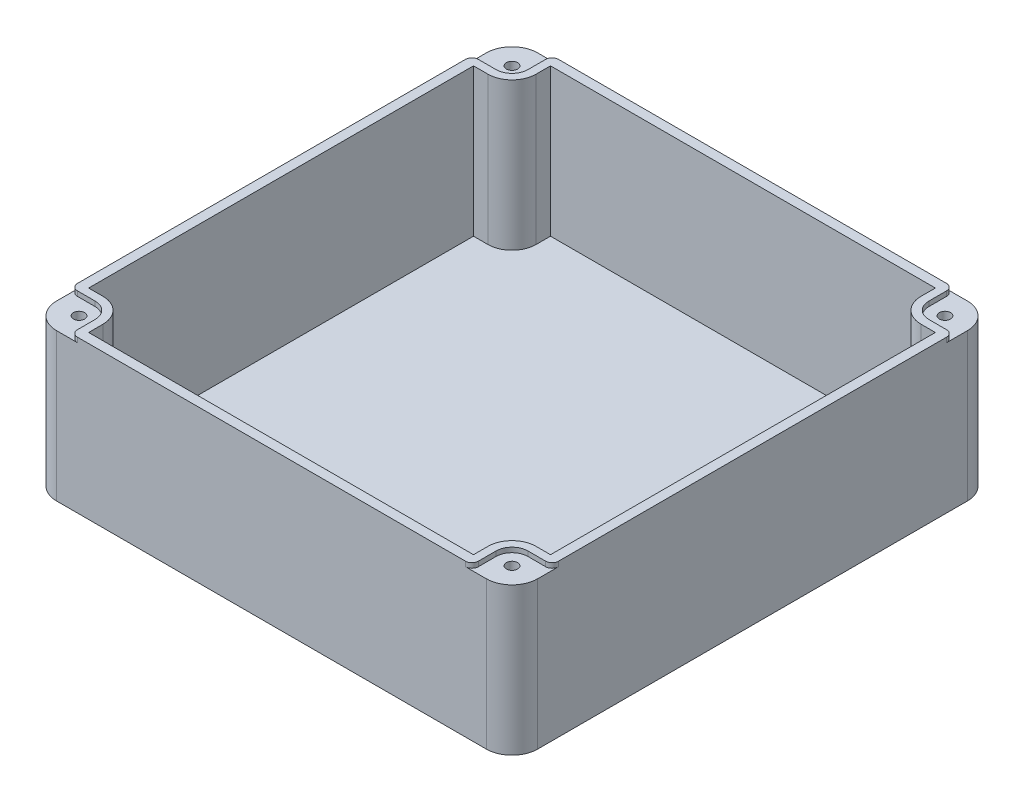
SolidWorks part; units mm, degrees
ref_plane "Front Plane" through (0, 0, 0) normal (0, 0, 1) x (1, 0, 0)
ref_plane "Top Plane" through (0, 0, 0) normal (0, 1, 0) x (1, 0, 0)
ref_plane "Right Plane" through (0, 0, 0) normal (1, 0, 0) x (0, 0, -1)
sketch "Sketch1" plane through (0, 0, 0) normal (0, 1, 0) x (1, 0, 0)
  line L0 (-72, -60) -> (-72, 60)
  line L1 (-67, -75) -> (67, -75)
  line L2 (-75, -67) -> (-75, 67)
  line L3 (-67, 75) -> (67, 75)
  line L4 (75, -67) -> (75, 67)
  line L5 (-75, -75) -> (75, 75) construction
  line L6 (-75, 75) -> (75, -75) construction
  line L7 (-60, 72) -> (60, 72)
  line L8 (72, -60) -> (72, 60)
  line L9 (-60, -72) -> (60, -72)
  line L10 (-62.5, 75) -> (-62.5, 67.5)
  line L11 (-67.5, 62.5) -> (-75, 62.5)
  line L12 (-67, 72) -> (67, 72) construction
  line L13 (-72, -67) -> (-72, 67) construction
  line L14 (-60, 72) -> (-60, 67.5)
  line L15 (-67.5, 60) -> (-72, 60)
  line L16 (62.5, 67.5) -> (62.5, 75)
  line L17 (75, 62.5) -> (67.5, 62.5)
  line L18 (72, 60) -> (67.5, 60)
  line L19 (60, 67.5) -> (60, 72)
  line L20 (67.5, -62.5) -> (75, -62.5)
  line L21 (62.5, -75) -> (62.5, -67.5)
  line L22 (60, -72) -> (60, -67.5)
  line L23 (67.5, -60) -> (72, -60)
  line L24 (-62.5, -67.5) -> (-62.5, -75)
  line L25 (-75, -62.5) -> (-67.5, -62.5)
  line L26 (-72, -60) -> (-67.5, -60)
  line L27 (-60, -67.5) -> (-60, -72)
  line L28 (-67.5, 62.5) -> (-72, 62.5) construction
  line L29 (72, -67) -> (72, 67) construction
  line L30 (-67, -72) -> (67, -72) construction
  line L31 (-62.5, 72) -> (-62.5, 67.5) construction
  arc A0 (-75, 67) -> (-67, 75) centre (-67, 67) cw
  arc A1 (67, 75) -> (75, 67) centre (67, 67) cw
  arc A2 (67, -75) -> (75, -67) centre (67, -67) ccw
  arc A3 (-67, -75) -> (-75, -67) centre (-67, -67) cw
  arc A4 (-62.5, 67.5) -> (-67.5, 62.5) centre (-67.5, 67.5) cw
  arc A5 (-60, 67.5) -> (-67.5, 60) centre (-67.5, 67.5) cw
  arc A6 (67.5, 62.5) -> (62.5, 67.5) centre (67.5, 67.5) cw
  arc A7 (67.5, 60) -> (60, 67.5) centre (67.5, 67.5) cw
  arc A8 (62.5, -67.5) -> (67.5, -62.5) centre (67.5, -67.5) cw
  arc A9 (60, -67.5) -> (67.5, -60) centre (67.5, -67.5) cw
  arc A10 (-67.5, -62.5) -> (-62.5, -67.5) centre (-67.5, -67.5) cw
  arc A11 (-67.5, -60) -> (-60, -67.5) centre (-67.5, -67.5) cw
  circle A12 centre (-67.5, 67.5) radius 1.75
  circle A13 centre (67.5, 67.5) radius 1.75
  circle A14 centre (67.5, -67.5) radius 1.75
  circle A15 centre (-67.5, -67.5) radius 1.75
  point P0 (0, 0)
  point P31 (-62.5, 62.5)
  point P70 (0, 0)
  dimension "D2" = 8
  dimension "D6" = 5
  dimension "D9" = 3.5
  dimension "D1" = 150
  dimension "D5" = 12.5
  dimension "D3" = 3
  dimension "D4" = 3
  dimension "D7" = 2.5
  dimension "D8" = 4
  dimension "D10" = 4
extrude "Boss-Extrude1" add sketch "Sketch1" against normal blind 46 contours L25 A10 L24 L1 L21 A8 L20 L4 L17 A6 L16 L3 L10 A4 L11 L2 A11 L26 L0 L15 A5 L14 L7 L19 A7 L18 L8 L23 A9 L22 L9 L27 | A8 L21 L1 A2 L4 L20 A14 | A10 L25 L2 A3 L1 L24 A15 | A4 L10 L3 A0 L2 L11 A12 | A6 L17 L4 A1 L3 L16 A13 | A14 | A15 | A12 | A13 region at (-72.5319, 0, 72.5319) region at (-60.3787, 0, 71.25) region at (62.6768, 0, 71.25) region at (-74.8232, 0, -64.75) region at (71.25, 0, -62.6768) region at (-67.5, 0, -67.5) region at (67.5, 0, 67.5) region at (-67.5, 0, 67.5)
extrude "Boss-Extrude2" add sketch "Sketch1<3>" along normal blind 1.5 contours L25 A10 L24 L1 L21 A8 L20 L4 L17 A6 L16 L3 L10 A4 L11 L2 A11 L26 L0 L15 A5 L14 L7 L19 A7 L18 L8 L23 A9 L22 L9 L27 region at (-60.3787, 0, 71.25)
sketch "Sketch1<3>" plane through (0, 0, 0) normal (0, 1, 0) x (1, 0, 0) same geometry as "Sketch1"
extrude "Cut-Extrude1" cut sketch "Sketch1<4>" against normal blind 13 contours A12 | A15 | A14 | A13 region at (-67.5, 0, -67.5) region at (-67.5, 0, 67.5)
sketch "Sketch1<4>" plane through (0, 0, 0) normal (0, 1, 0) x (1, 0, 0) same geometry as "Sketch1"
sketch "Sketch2" plane through (0, -46, 0) normal (0, -1, 0) x (1, 0, 0)
  line L4 (-75, 67) -> (-75, -67)
  line L5 (-67, -75) -> (67, -75)
  line L6 (75, -67) -> (75, 67)
  line L7 (67, 75) -> (-67, 75)
  line L8 (-75, 67) -> (-75, -67)
  line L9 (-67, -75) -> (67, -75)
  line L10 (75, -67) -> (75, 67)
  line L11 (67, 75) -> (-67, 75)
  arc A4 (-75, -67) -> (-67, -75) centre (-67, -67) ccw
  arc A5 (67, -75) -> (75, -67) centre (67, -67) ccw
  arc A6 (75, 67) -> (67, 75) centre (67, 67) ccw
  arc A7 (-67, 75) -> (-75, 67) centre (-67, 67) ccw
  arc A8 (-75, -67) -> (-67, -75) centre (-67, -67) ccw
  arc A9 (67, -75) -> (75, -67) centre (67, -67) ccw
  arc A10 (75, 67) -> (67, 75) centre (67, 67) ccw
  arc A11 (-67, 75) -> (-75, 67) centre (-67, 67) ccw
  dimension "D1" = 0
extrude "Boss-Extrude3" add sketch "Sketch2" against normal blind 1.5
fillet "Fillet1" radius 2 8 edges at (62.5, 0.75, -75) (75, 0.75, -62.5) (75, 0.75, 62.5) (62.5, 0.75, 75) (-62.5, 0.75, 75) (-75, 0.75, 62.5) (-75, 0.75, -62.5) (-62.5, 0.75, -75)
